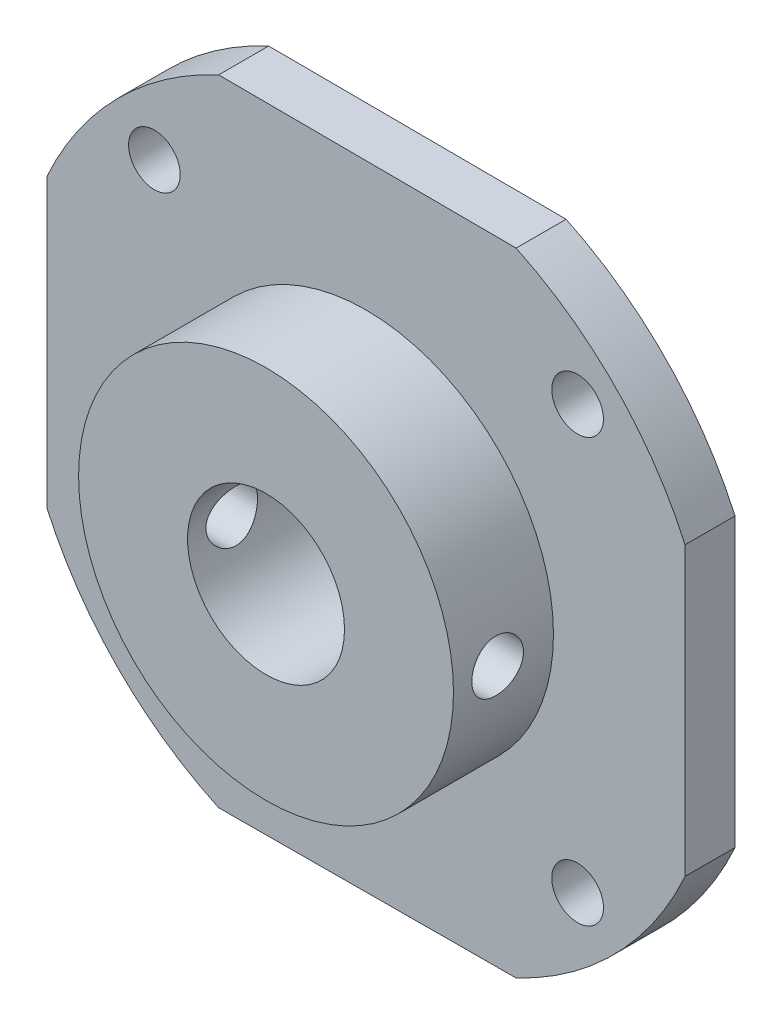
SolidWorks part; units mm, degrees
ref_plane "Front" through (0, 0, 0) normal (0, 0, 1) x (1, 0, 0)
ref_plane "Top" through (0, 0, 0) normal (0, 1, 0) x (1, 0, 0)
ref_plane "Right" through (0, 0, 0) normal (1, 0, 0) x (0, 0, -1)
sketch "Sketch1" plane through (0, 0, 0) normal (0, 0, 1) x (1, 0, 0)
  circle A0 centre (22.225, 22.225) radius 21
extrude "Extrude1" add sketch "Sketch1" along normal blind 3
sketch "Sketch2" plane through (0, 0, 3) normal (0, 0, 1) x (1, 0, 0)
  circle A0 centre (22.225, 22.225) radius 11.25
extrude "Extrude2" add sketch "Sketch2" along normal blind 6
sketch "Sketch3" plane through (0, 0, 0) normal (1, 0, 0) x (0, 0, -1)
  line L0 (-9, 22.225) -> (-3, 22.225) construction
  circle A0 centre (-6.35, 22.225) radius 1.55
extrude "Cut-Extrude1" cut sketch "Sketch3" along normal blind 44.45
sketch "Sketch4" plane through (0, 0, 3) normal (0, 0, 1) x (1, 0, 0)
  circle A0 centre (34.925, 34.925) radius 1.55
  circle A1 centre (9.525, 34.925) radius 1.55
  circle A2 centre (34.925, 9.525) radius 1.55
  circle A3 centre (9.525, 9.525) radius 1.55
extrude "Cut-Extrude2" cut sketch "Sketch4" against normal through all
sketch "Sketch5" plane through (0, 0, 9) normal (0, 0, 1) x (1, 0, 0)
  circle A0 centre (22.225, 22.225) radius 4.71
extrude "Cut-Extrude3" cut sketch "Sketch5" against normal through all
sketch "Sketch6" plane through (0, 0, 0) normal (0, 0, -1) x (-1, 0, 0)
  line L0 (-41.375, 31.75) -> (-41.375, 12.7)
  line L1 (-3.075, 31.75) -> (-3.075, 12.7)
  line L2 (-33.475, 22.225) -> (-26.935, 22.225) construction
  line L3 (-12.7, 41.275) -> (-31.6507, 41.1923)
  line L4 (-12.7, 3.175) -> (-31.6507, 3.2577)
  arc A0 (-12.7, 41.275) -> (-31.6507, 41.1923) centre (-22.0924, 22.225) ccw
  arc A1 (-41.375, 31.75) -> (-41.375, 12.7) centre (-22.0924, 22.225) ccw
  arc A2 (-3.075, 12.7) -> (-3.075, 31.75) centre (-22.0924, 22.225) ccw
  arc A3 (-12.7, 3.175) -> (-31.6507, 3.2577) centre (-22.0924, 22.225) cw
extrude "Cut-Extrude7" cut sketch "Sketch6" against normal through all
